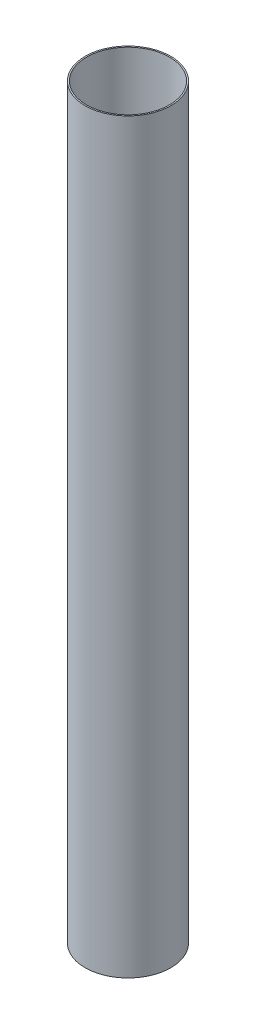
SolidWorks part; units mm, degrees
material "E-Glass Fiber"
ref_plane "Front Plane" through (0, 0, 0) normal (0, 0, 1) x (1, 0, 0)
ref_plane "Top Plane" through (0, 0, 0) normal (0, 1, 0) x (1, 0, 0)
ref_plane "Right Plane" through (0, 0, 0) normal (1, 0, 0) x (0, 0, -1)
sketch "Sketch1" plane through (0, 0, 0) normal (0, 1, 0) x (1, 0, 0)
  circle A0 centre (0, 0) radius 39.37
  circle A1 centre (0, 0) radius 38.1
  dimension "D1" = 78.74
  dimension "D2" = 76.2
extrude "Boss-Extrude2" add sketch "Sketch1" along normal blind 685.8
